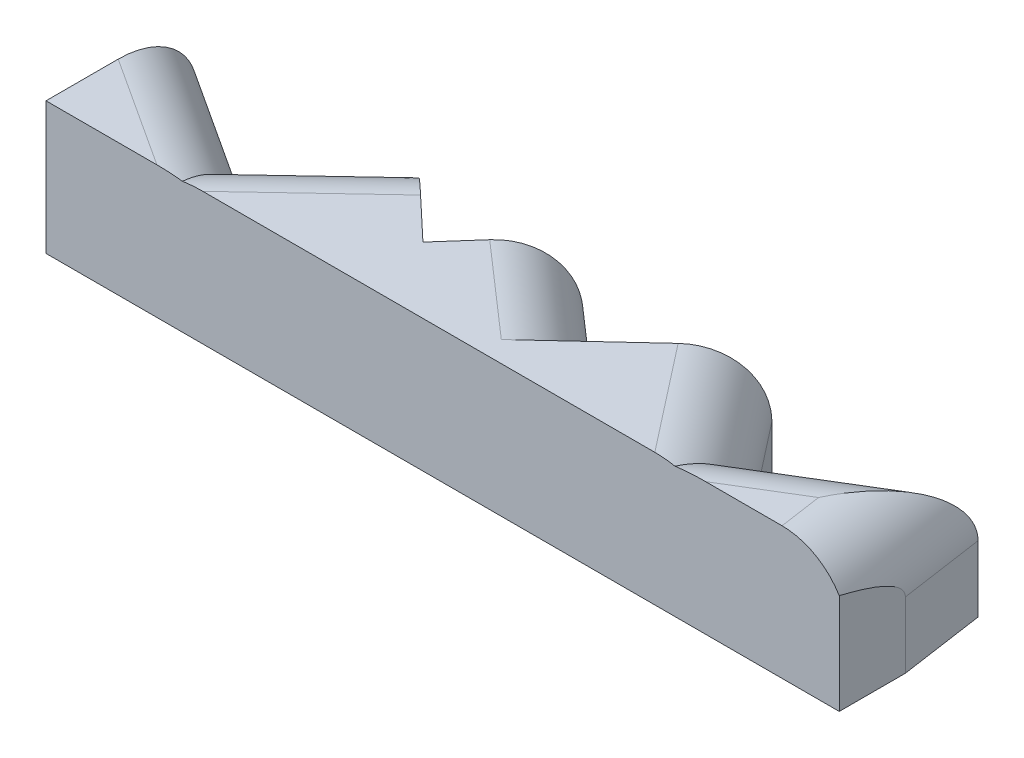
SolidWorks part; units mm, degrees
ref_plane "Front Plane" through (0, 0, 0) normal (0, 0, 1) x (1, 0, 0)
ref_plane "Top Plane" through (0, 0, 0) normal (0, 1, 0) x (1, 0, 0)
ref_plane "Right Plane" through (0, 0, 0) normal (1, 0, 0) x (0, 0, -1)
sketch "Sketch1" plane through (0, 129.5222, 0) normal (0, 1, 0) x (1, 0, 0)
  line L0 (120.0519, -70.0763) -> (120.0519, -19.2763) construction
  line L1 (-32.3481, -19.2763) -> (120.0519, -19.2763)
  line L2 (-32.3481, -19.2763) -> (-32.3481, -6.5763)
  line L3 (-32.3481, -6.5763) -> (120.0519, -6.5763)
  line L4 (120.0519, -19.2763) -> (120.0519, -6.5763)
  dimension "D1" = 12.7
extrude "Boss-Extrude1" add sketch "Sketch1" against normal up to surface (25.4 mm away)
sketch "Sketch2" plane through (0, 129.5222, 0) normal (0, 1, 0) x (1, 0, 0)
  line L0 (-32.3481, -6.5763) -> (-32.3481, 9.752)
  line L1 (-32.3481, 9.752) -> (-7.2688, -6.5763)
  line L2 (-7.2688, -6.5763) -> (10.0577, 9.752)
  line L3 (10.0577, 9.752) -> (27.3702, -6.5763)
  line L4 (27.3702, -6.5763) -> (41.7906, 9.752)
  line L5 (41.7906, 9.752) -> (60.4723, -6.5763)
  line L6 (60.4723, -6.5763) -> (78.079, 9.752)
  line L7 (78.079, 9.752) -> (90.818, -6.5763)
  line L8 (90.818, -6.5763) -> (117.6787, 9.752)
  line L9 (117.6787, 9.752) -> (120.0519, -6.5763)
  line L12 (120.0519, -6.5763) -> (-32.3481, -6.5763) construction
  line L13 (-32.3481, -6.5763) -> (-32.3481, -19.2763) construction
  line L15 (120.0519, -6.5763) -> (120.0519, -10.4966)
  line L16 (120.0519, -10.4966) -> (-32.3481, -10.4966)
  line L17 (-32.3481, -6.5763) -> (-32.3481, -10.4966)
extrude "Boss-Extrude2" add sketch "Sketch2" against normal up to surface (25.4 mm away)
fillet "Fillet1" [suppressed] radius 2.54
fillet "Fillet2" radius 12.7 6 edges at (-19.8085, 129.5222, -1.5879) (1.3945, 129.5222, -1.5879) (118.8653, 129.5222, -1.5879) (104.2483, 129.5222, -1.5879) (84.4485, 129.5222, -1.5879) (51.1315, 129.5222, -1.5879)
ref_plane "Print-base" through (0, 104.1222, 0) normal (0, -1, 0) x (-1, 0, 0)
